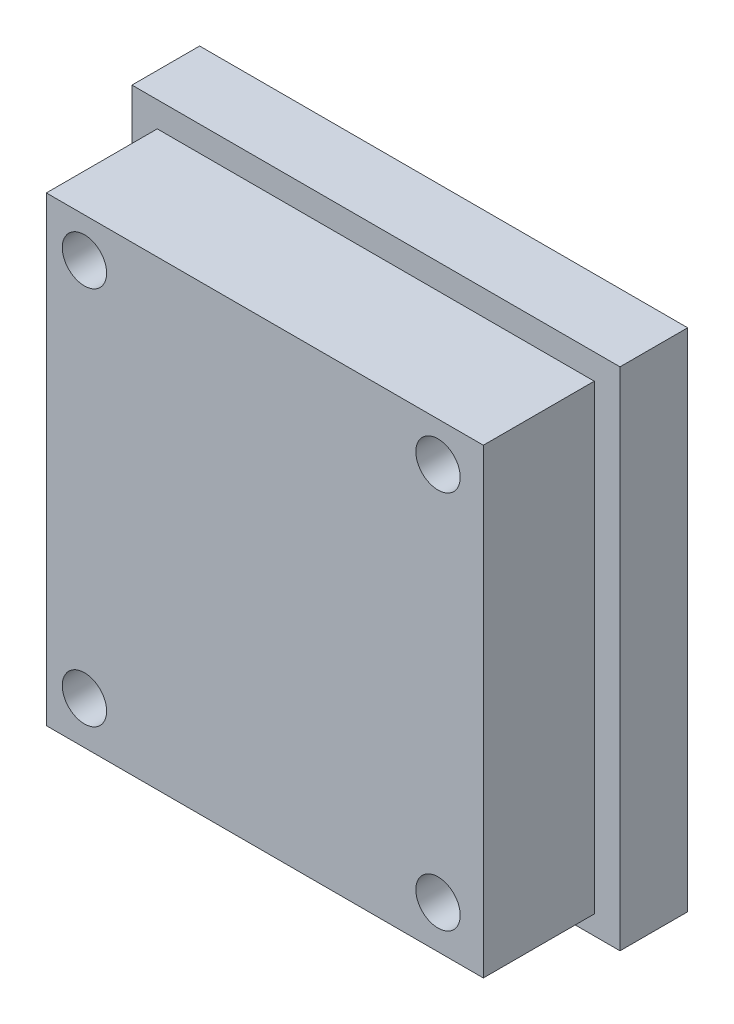
SolidWorks part; units mm, degrees
ref_plane "Front Plane" through (0, 0, 0) normal (0, 0, 1) x (1, 0, 0)
ref_plane "Top Plane" through (0, 0, 0) normal (0, 1, 0) x (1, 0, 0)
ref_plane "Right Plane" through (0, 0, 0) normal (1, 0, 0) x (0, 0, -1)
sketch "Sketch1" plane through (0, 0, 0) normal (0, 0, 1) x (1, 0, 0)
  line L1 (-26.34, 21.9) -> (17.66, 21.9)
  line L2 (-26.34, 21.9) -> (-26.34, -23.7)
  line L3 (-26.34, -23.7) -> (17.66, -23.7)
  line L4 (17.66, 21.9) -> (17.66, -23.7)
  line L5 (-24.06, 19.62) -> (15.34, 19.62)
  line L6 (-24.06, 19.62) -> (-24.06, -21.98)
  line L7 (-24.06, -21.98) -> (15.34, -21.98)
  line L8 (15.34, 19.62) -> (15.34, -21.98)
  dimension "D1" = 45.6
  dimension "D2" = 44
  dimension "D3" = 39.4
  dimension "D4" = 41.6
extrude "Boss-Extrude1" add sketch "Sketch1" along normal blind 16.1 contours L6 L7 L8 L5
extrude "Boss-Extrude2" add sketch "Sketch1<3>" along normal blind 6.1
sketch "Sketch1<3>" plane through (0, 0, 0) normal (0, 0, 1) x (1, 0, 0) same geometry as "Sketch1"
sketch "Sketch2" plane through (0, 0, 16.1) normal (0, 0, 1) x (1, 0, 0)
  circle A0 centre (-20.624, -18.1252) radius 2
  circle A1 centre (-20.624, 16.0742) radius 2
  circle A2 centre (11.2537, 16.0742) radius 2
  circle A3 centre (11.2537, -18.1252) radius 2
  dimension "D1" = 4
  dimension "D2" = 4
  dimension "D3" = 4
  dimension "D4" = 4
extrude "Cut-Extrude1" cut sketch "Sketch2" against normal through all
